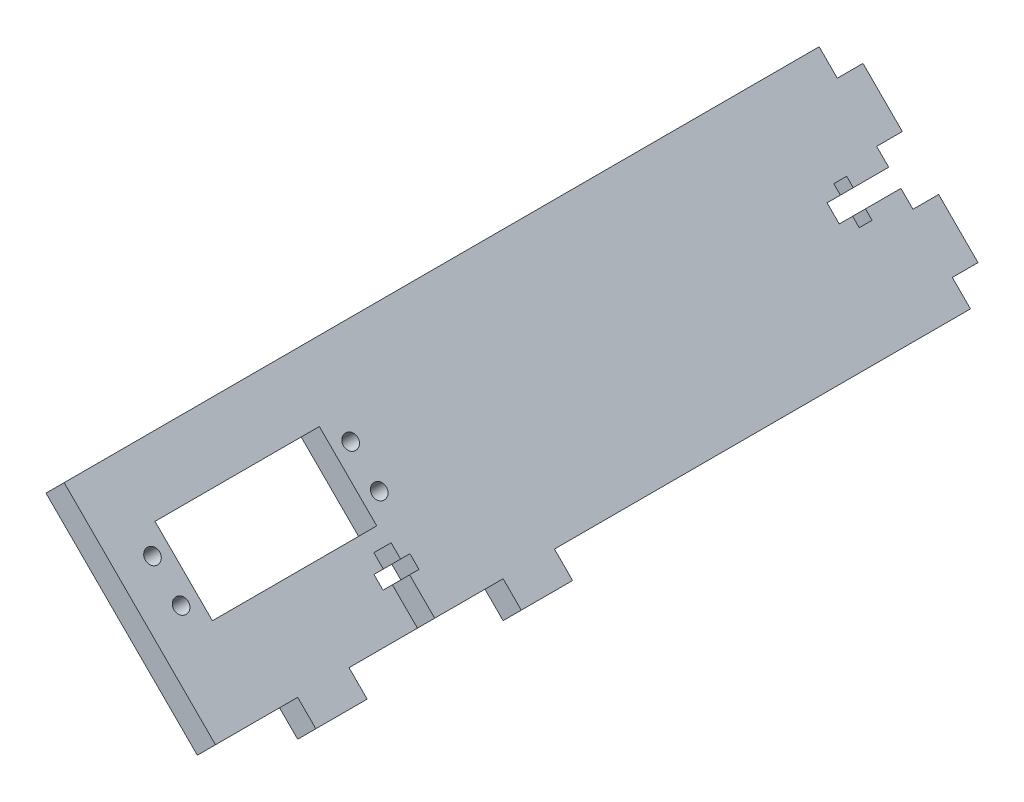
SolidWorks part; units mm, degrees
ref_plane "Front Plane" through (0, 0, 0) normal (0, 0, 1) x (1, 0, 0)
ref_plane "Top Plane" through (0, 0, 0) normal (0, 1, 0) x (1, 0, 0)
ref_plane "Right Plane" through (0, 0, 0) normal (1, 0, 0) x (0, 0, -1)
sketch "Sketch2" plane through (0, 0, 0) normal (0, 0, 1) x (1, 0, 0)
  line L0 (-71.1005, 3.7485) -> (-75.5906, -0.7416)
  line L1 (-71.1005, 3.7485) -> (-42.6562, -24.6957)
  line L2 (-75.5906, -0.7416) -> (-47.1463, -29.1858)
  line L3 (-42.6562, -24.6957) -> (-47.1463, -29.1858)
  line L4 (-75.5906, -0.7416) -> (-65.8586, -10.4736) construction
  line L5 (-61.3685, -5.9835) -> (-71.1005, 3.7485) construction
  line L6 (-47.1463, -29.1858) -> (-42.6562, -24.6957) construction
  line L7 (-71.1005, 3.7485) -> (-75.5906, -0.7416) construction
extrude "Base Extrusion" add sketch "Sketch2" along normal blind 186.69
sketch "Sketch3" plane through (-38.1661, -38.1661, 0) normal (-0.7071, -0.7071, 0) x (0, 0, 1)
  line L0 (0, 32.8131) -> (24.1393, 32.8131) construction
  line L1 (0, 52.9262) -> (0, 12.7) construction
  line B0 (0, 34.9467) -> (0, 30.6795)
  line B1 (11.938, 30.6795) -> (11.938, 28.3681)
  line B2 (11.938, 28.3681) -> (8.763, 28.3681)
  line B3 (8.763, 28.3681) -> (8.763, 30.6795)
  line B4 (8.763, 30.6795) -> (0, 30.6795)
  line B5 (11.938, 30.6795) -> (15.24, 30.6795)
  line B6 (15.24, 30.6795) -> (15.24, 34.9467)
  line B7 (11.938, 34.9467) -> (15.24, 34.9467)
  line B8 (8.763, 34.9467) -> (0, 34.9467)
  line B9 (8.763, 37.2581) -> (8.763, 34.9467)
  line B10 (11.938, 37.2581) -> (8.763, 37.2581)
  line B11 (11.938, 34.9467) -> (11.938, 37.2581)
sketch_block_instance "TSlot-1"
sketch_block "TSlot" parameters "D1"=3.302, "D2"=3.175
extrude "Base T Slot" cut sketch "Sketch3" against normal through all
sketch "Sketch4" plane through (0, 0, 0) normal (0, 0, -1) x (-1, 0, 0)
  line L0 (75.5906, -0.7416) -> (65.8586, -10.4736) construction
  line L1 (65.8586, -10.4736) -> (61.3685, -5.9835) construction
  line L2 (61.3685, -5.9835) -> (71.1005, 3.7485) construction
  line L3 (71.1005, 3.7485) -> (75.5906, -0.7416) construction
  line L4 (42.6562, -24.6957) -> (52.3882, -14.9637) construction
  line L5 (52.3882, -14.9637) -> (56.8783, -19.4538) construction
  line L6 (56.8783, -19.4538) -> (47.1463, -29.1858) construction
  line L7 (47.1463, -29.1858) -> (42.6562, -24.6957) construction
  line L8 (75.5906, -0.7416) -> (65.8586, -10.4736)
  line L9 (65.8586, -10.4736) -> (61.3685, -5.9835)
  line L10 (61.3685, -5.9835) -> (71.1005, 3.7485)
  line L11 (71.1005, 3.7485) -> (75.5906, -0.7416)
  line L12 (42.6562, -24.6957) -> (52.3882, -14.9637)
  line L13 (52.3882, -14.9637) -> (56.8783, -19.4538)
  line L14 (56.8783, -19.4538) -> (47.1463, -29.1858)
  line L15 (47.1463, -29.1858) -> (42.6562, -24.6957)
extrude "Base Tabs" add sketch "Sketch4" along normal blind 6.35
sketch "Sketch5" plane through (-33.676, -33.676, 0) normal (0.7071, 0.7071, 0) x (0, 0, -1)
  line L1 (-173.99, 45.466) -> (-133.35, 45.466)
  line L2 (-173.99, 45.466) -> (-173.99, 25.4)
  line L3 (-173.99, 25.4) -> (-133.35, 25.4)
  line L4 (-133.35, 45.466) -> (-133.35, 25.4)
  line L5 (-186.69, 12.7) -> (-186.69, 52.9262) construction
  line L6 (-165.1552, 45.466) -> (-139.1365, 45.466) construction
  line L7 (-139.1365, 25.4) -> (-164.2745, 25.4) construction
  line L8 (-165.1552, 45.466) -> (-139.1365, 45.466) construction
  line L9 (-139.1365, 25.4) -> (-164.2745, 25.4) construction
  dimension "D1" = 40.64
  dimension "D2" = 12.7
extrude "Servo Slot" cut sketch "Sketch5" against normal through all
sketch "Sketch6" plane through (-33.676, -33.676, 0) normal (0.7071, 0.7071, 0) x (0, 0, -1)
  arc A4 (-179.4143, 39.163) -> (-179.4143, 41.703) centre (-178.17, 40.433) ccw construction
  arc A5 (-179.4143, 29.163) -> (-179.4143, 31.703) centre (-178.17, 30.433) ccw construction
  arc A6 (-127.9257, 41.703) -> (-127.9257, 39.163) centre (-129.17, 40.433) ccw construction
  arc A7 (-127.9257, 31.703) -> (-127.9257, 29.163) centre (-129.17, 30.433) ccw construction
  circle A8 centre (-178.17, 40.433) radius 1.778
  circle A9 centre (-178.17, 30.433) radius 1.778
  circle A10 centre (-129.17, 40.433) radius 1.778
  circle A11 centre (-129.17, 30.433) radius 1.778
extrude "Servo Mounting Holes" cut sketch "Sketch6" against normal through all
sketch "Sketch7" plane through (0, 0, 186.69) normal (0, 0, 1) x (1, 0, 0)
  line L0 (-47.1463, -29.1858) -> (-42.6562, -24.6957)
  line L1 (-47.1463, -29.1858) -> (-42.6562, -33.676)
  line L2 (-42.6562, -24.6957) -> (-38.1661, -29.1858)
  line L3 (-42.6562, -33.676) -> (-38.1661, -29.1858)
  line L4 (-92.784, -83.8038) -> (-85.6806, -76.7004) construction
  line L5 (-75.5906, -0.7416) -> (-71.1005, 3.7485)
  line L6 (-75.5906, -0.7416) -> (-80.0807, 3.7485)
  line L7 (-71.1005, 3.7485) -> (-75.5906, 8.2387)
  line L8 (-80.0807, 3.7485) -> (-75.5906, 8.2387)
extrude "Filler Extrusion to Funnel Support" add sketch "Sketch7" against normal up to surface (186.69 mm away)
sketch "Sketch8" plane through (-33.676, -33.676, 0) normal (0.7071, 0.7071, 0) x (0.7071, -0.7071, 0)
  line L0 (28.1183, -134.62) -> (-82.975, -134.62) construction
  line L1 (-9.6878, -82.55) -> (7.2286, -82.55) construction
  line L2 (-6.35, -186.69) -> (-59.2762, -186.69) construction
  line L3 (-6.35, -186.69) -> (-6.35, -166.37) construction
  line B0 (-6.35, -136.7536) -> (-6.35, -132.4864)
  line B1 (-18.288, -132.4864) -> (-18.288, -130.175)
  line B2 (-18.288, -130.175) -> (-15.113, -130.175)
  line B3 (-15.113, -130.175) -> (-15.113, -132.4864)
  line B4 (-15.113, -132.4864) -> (-6.35, -132.4864)
  line B5 (-18.288, -132.4864) -> (-21.59, -132.4864)
  line B6 (-21.59, -132.4864) -> (-21.59, -136.7536)
  line B7 (-18.288, -136.7536) -> (-21.59, -136.7536)
  line B8 (-15.113, -136.7536) -> (-6.35, -136.7536)
  line B9 (-15.113, -139.065) -> (-15.113, -136.7536)
  line B10 (-18.288, -139.065) -> (-15.113, -139.065)
  line B11 (-18.288, -136.7536) -> (-18.288, -139.065)
sketch_block_instance "TSlot-2"
extrude "Side T Slot" cut sketch "Sketch8" against normal through all
sketch "Sketch9" plane through (-4.4901, 4.4901, 0) normal (0.7071, -0.7071, 0) x (-0.7071, -0.7071, 0)
  line L0 (49.5253, -247.9715) -> (49.5253, -199.7444) construction
  line L1 (53.975, -136.7536) -> (53.975, -186.69) construction
  line L2 (53.975, -166.37) -> (47.625, -166.37)
  line L3 (53.975, -166.37) -> (53.975, -153.67)
  line L4 (53.975, -153.67) -> (47.625, -153.67)
  line L5 (47.625, -166.37) -> (47.625, -153.67)
  line L6 (47.625, -136.7536) -> (47.625, -186.69) construction
  line L7 (53.975, 0) -> (53.975, -132.4864) construction
  line L8 (53.975, -115.57) -> (47.625, -115.57)
  line L9 (53.975, -115.57) -> (53.975, -102.87)
  line L10 (53.975, -102.87) -> (47.625, -102.87)
  line L11 (47.625, -115.57) -> (47.625, -102.87)
  line L12 (47.625, 0) -> (47.625, -132.4864) construction
  line L13 (104.7498, -134.62) -> (30.8469, -134.62) construction
  line L14 (53.975, -186.69) -> (47.625, -186.69) construction
  line L15 (29.2312, -82.55) -> (47.625, -82.55) construction
  dimension "D1" = 12.7
  dimension "D2" = 19.05
extrude "Side Tabs" add sketch "Sketch9" along normal up to surface (6.35 mm away)
